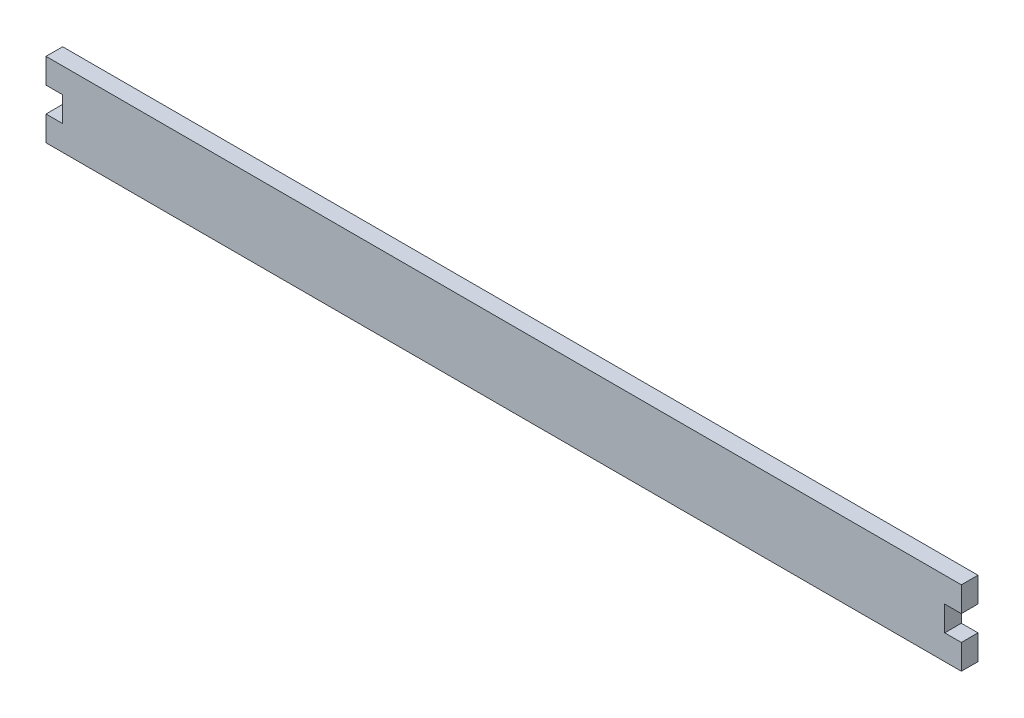
SolidWorks part; units mm, degrees
material "Teak"
ref_plane "Front Plane" through (0, 0, 0) normal (0, 0, 1) x (1, 0, 0)
ref_plane "Top Plane" through (0, 0, 0) normal (0, 1, 0) x (1, 0, 0)
ref_plane "Right Plane" through (0, 0, 0) normal (1, 0, 0) x (0, 0, -1)
sketch "Sketch1" plane through (0, 0, 0) normal (0, 0, 1) x (1, 0, 0)
  line L1 (-275, 22.5) -> (275, 22.5)
  line L2 (-275, 22.5) -> (-275, -22.5)
  line L3 (-275, -22.5) -> (275, -22.5)
  line L4 (275, 22.5) -> (275, -22.5)
  line L5 (-275, 22.5) -> (275, -22.5) construction
  line L6 (-275, -22.5) -> (275, 22.5) construction
  point P0 (0, 0)
  dimension "D1" = 550
  dimension "D2" = 45
extrude "Основа" add sketch "Sketch1" along normal blind 10
sketch "Sketch2" plane through (0, 0, 10) normal (0, 0, 1) x (1, 0, 0)
  line L0 (-275, -7.5) -> (-265, -7.5)
  line L1 (-275, 22.5) -> (-275, -22.5) construction
  line L2 (-265, -7.5) -> (-265, 7.5)
  line L3 (-265, 7.5) -> (-275, 7.5)
  line L4 (-275, 7.5) -> (-275, -7.5)
  line L5 (0, 22.5) -> (0, -22.5) construction
  line L6 (275, 22.5) -> (-275, 22.5) construction
  line L7 (-275, -22.5) -> (275, -22.5) construction
  point P13 (-275, 0)
  point P14 (-275, 0)
  dimension "D1" = 10
  dimension "D2" = 15
extrude "Шип" cut sketch "Sketch2" against normal up to next
sketch "Sketch3" plane through (0, 0, 10) normal (0, 0, 1) x (1, 0, 0)
  line L0 (-265, 7.5) -> (-275, 7.5) construction
  line L1 (-275, 22.5) -> (-275, 7.5) construction
  line L2 (-275, -7.5) -> (-275, -22.5) construction
  circle A0 centre (-270, 15) radius 1.75
  circle A1 centre (-270, -15) radius 1.75
  point P7 (-270, 7.5)
  point P12 (-275, 15)
  point P16 (-275, -15)
  dimension "D1" = 3.5
extrude "Крепежные" [suppressed] cut sketch "Sketch3" against normal up to next
mirror "Mirror1" about plane through (0, 0, 0) normal (1, 0, 0) of "Крепежные", "Шип"
